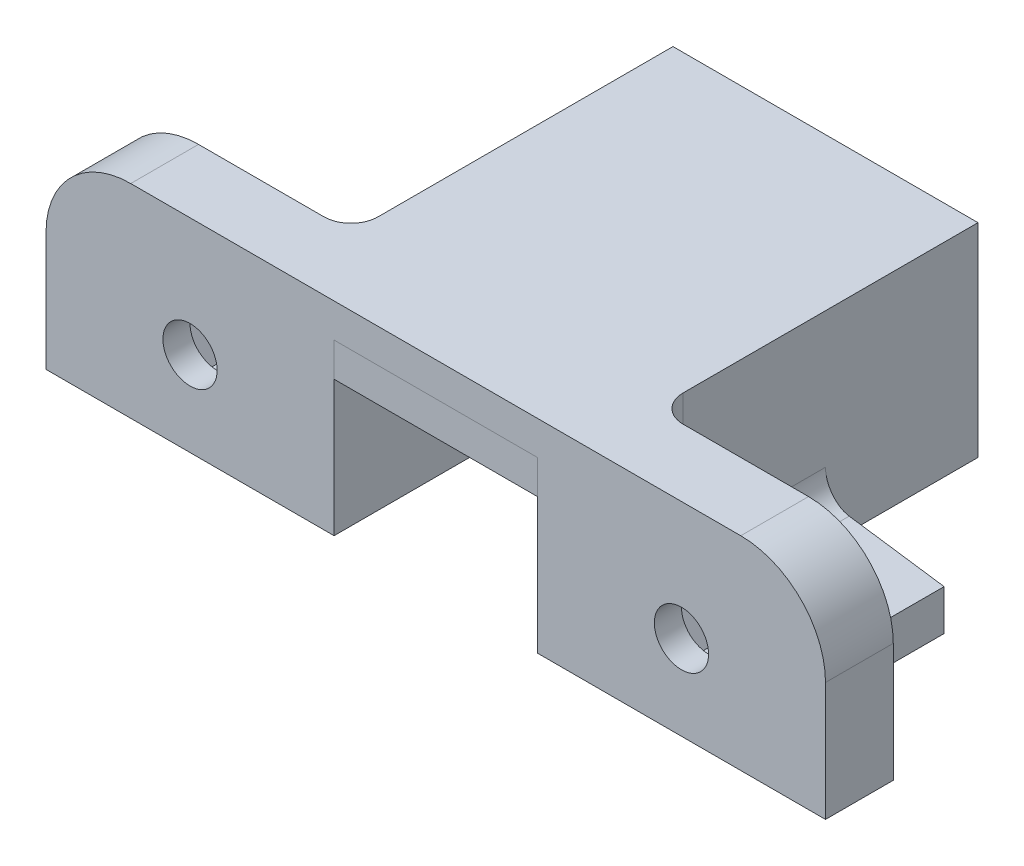
SolidWorks part; units mm, degrees
ref_plane "Front Plane" through (0, 0, 0) normal (0, 0, 1) x (1, 0, 0)
ref_plane "Top Plane" through (0, 0, 0) normal (0, 1, 0) x (1, 0, 0)
ref_plane "Right Plane" through (0, 0, 0) normal (1, 0, 0) x (0, 0, -1)
sketch "Sketch1" plane through (0, 0, 0) normal (0, 1, 0) x (1, 0, 0)
  line L0 (-23, 0) -> (23, 0)
  line L1 (23, 0) -> (23, 4)
  line L2 (23, 4) -> (9, 4)
  line L3 (9, 4) -> (9, 23)
  line L4 (9, 23) -> (-9, 23)
  line L5 (-9, 23) -> (-9, 4)
  line L6 (-9, 4) -> (-23, 4)
  line L7 (-23, 4) -> (-23, 0)
  point P7 (0, 0)
  dimension "D1" = 4
  dimension "D2" = 46
  dimension "D3" = 23
  dimension "18" = 18
extrude "Boss-Extrude1" add sketch "Sketch1" along normal blind 12
sketch "Sketch2" plane through (0, 0, 0) normal (0, 0, 1) x (1, 0, 0)
  line L0 (-23, 0) -> (23, 0) construction
  line L1 (-6, 0) -> (6, 0)
  line L2 (-6, 0) -> (-6, 10)
  line L3 (-6, 10) -> (6, 10)
  line L4 (6, 0) -> (6, 10)
  point P6 (0, 10)
  dimension "D1" = 12
  dimension "D2" = 10
extrude "Cut-Extrude1" cut sketch "Sketch2" against normal blind 10.2
sketch "Sketch3" plane through (0, 0, -10.2) normal (0, 0, 1) x (1, 0, 0)
  line L0 (0, -55) -> (0, 55) construction
  line L1 (-6, 0) -> (6, 0)
  line L2 (-6, 0) -> (-6, 6.562)
  line L3 (-3.6661, 10) -> (3.6661, 10)
  line L4 (6, 0) -> (6, 6.562)
  line L5 (-6, 0) -> (-6, 10) construction
  line L6 (-6, 10) -> (6, 10) construction
  arc A0 (6, 6.562) -> (3.6661, 10) centre (0, 5) ccw
  arc A1 (-6, 6.562) -> (-3.6661, 10) centre (0, 5) cw
  point P19 (-6, 5)
  dimension "D1" = 6.2
extrude "Cut-Extrude2" cut sketch "Sketch3" against normal through all
sketch "Sketch4" plane through (0, 0, 0) normal (0, 0, 1) x (1, 0, 0)
  line L0 (6, 6.562) -> (6, 10) construction
  line L1 (-6, 10) -> (6, 10)
  line L2 (-6, 10) -> (-6, 8)
  line L3 (-6, 8) -> (6, 8)
  line L4 (6, 10) -> (6, 8)
  dimension "D1" = 2
extrude "Boss-Extrude2" add sketch "Sketch4" against normal blind 0.8 separate body
sketch "Sketch5" plane through (0, 0, 0) normal (0, 0, 1) x (1, 0, 0)
  line L0 (-14.5, 5) -> (14.5, 5) construction
  line L1 (-23, 0) -> (-6, 0) construction
  circle A0 centre (-14.5, 5) radius 1.6
  circle A1 centre (14.5, 5) radius 1.6
  point P2 (0, 5)
  dimension "D2" = 3.2
  dimension "D1" = 29
  dimension "D3" = 5
extrude "Cut-Extrude3" cut sketch "Sketch5" against normal through all
sketch "Sketch6" plane through (0, 0, 0) normal (0, -1, 0) x (1, 0, 0)
  line L29 (-9, -14) -> (-9, -4)
  line L30 (-9, -23) -> (-9, -4) construction
  line L31 (-9, -4) -> (-17, -4)
  line L32 (-17, -4) -> (-17, -13)
  line L33 (-17, -13) -> (-9, -14)
  line L34 (0, -6.6) -> (0, 6.6) construction
  line L35 (17, -13) -> (9, -14)
  line L36 (17, -4) -> (17, -13)
  line L37 (9, -4) -> (17, -4)
  line L38 (9, -14) -> (9, -4)
  line L43 (-9, -4) -> (-23, -4) construction
  point P9 (-9, -9)
  dimension "D5" = 9
  dimension "D6" = 8
  dimension "D7" = 9
extrude "Boss-Extrude3" add sketch "Sketch6" against normal blind 2.4
fillet "Fillet1" radius 1.6 6 edges at (9, 7.2, -4) (-9, 7.2, -4) (-9, 2.4, -9) (9, 2.4, -9) (-13, 2.4, -4) (13, 2.4, -4)
sketch "Sketch8" plane through (0, 0, -4) normal (0, 0, -1) x (-1, 0, 0)
  line L7 (16.2321, 2) -> (17.9641, 5)
  line L8 (17.9641, 5) -> (16.2321, 8)
  line L9 (16.2321, 8) -> (12.7679, 8)
  line L10 (12.7679, 8) -> (11.0359, 5)
  line L11 (11.0359, 5) -> (12.7679, 2)
  line L12 (12.7679, 2) -> (16.2321, 2)
  line L13 (-12.7679, 2) -> (-11.0359, 5)
  line L14 (-11.0359, 5) -> (-12.7679, 8)
  line L15 (-12.7679, 8) -> (-16.2321, 8)
  line L16 (-16.2321, 8) -> (-17.9641, 5)
  line L17 (-17.9641, 5) -> (-16.2321, 2)
  line L18 (-16.2321, 2) -> (-12.7679, 2)
  circle A0 centre (-14.5, 5) radius 3 construction
  circle A1 centre (14.5, 5) radius 3 construction
  dimension "D1" = 6
extrude "Cut-Extrude5" cut sketch "Sketch8" against normal blind 2.4 and the other way blind 2.5
fillet "Fillet2" radius 5 2 edges at (23, 12, -2) (-23, 12, -2)
sketch "Sketch9" plane through (0, 2.4, 0) normal (0, 1, 0) x (1, 0, 0)
  line L0 (-18, 0) -> (18, 0) construction
  line L1 (0, -6.6) -> (0, 6.6) construction
  circle A0 centre (-13, 8.5) radius 1.6
  circle A1 centre (13, 8.5) radius 1.6
  dimension "D3" = 3.2
  dimension "D1" = 13
  dimension "D2" = 8.5
extrude "Cut-Extrude6" cut sketch "Sketch9" against normal up to next (2.4 mm away)
